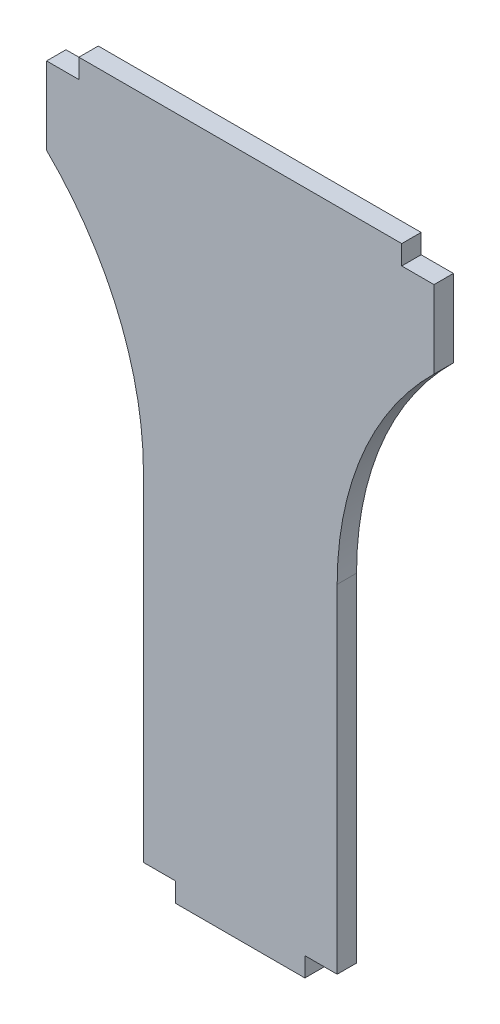
SolidWorks part; units mm, degrees
material "Acrylic (Medium-high impact)"
ref_plane "Plano frontal" through (0, 0, 0) normal (0, 0, 1) x (1, 0, 0)
ref_plane "Plano superior" through (0, 0, 0) normal (0, 1, 0) x (1, 0, 0)
ref_plane "Plano direito" through (0, 0, 0) normal (1, 0, 0) x (0, 0, -1)
sketch "Sketch2" plane through (0, 0, 0) normal (0, 0, 1) x (1, 0, 0)
  line L0 (15, 44) -> (30, 44)
  line L1 (10, -44) -> (15, -44)
  line L2 (-15, 44) -> (-15, -44)
  line L3 (-15, -44) -> (-10, -44)
  line L4 (15, 44) -> (15, -44)
  line L5 (-15, 44) -> (15, -44) construction
  line L6 (-15, -44) -> (15, 44) construction
  line L7 (-30, 56) -> (-25, 56)
  line L8 (-30, 56) -> (-30, 44)
  line L9 (-30, 44) -> (-15, 44)
  line L10 (30, 56) -> (30, 44)
  line L11 (-25, 59) -> (25, 59)
  line L12 (-25, 59) -> (-25, 56)
  line L14 (25, 59) -> (25, 56)
  line L16 (-10, -44) -> (-10, -47)
  line L17 (-10, -47) -> (10, -47)
  line L18 (10, -44) -> (10, -47)
  line L19 (25, 56) -> (30, 56)
  point P0 (0, 0)
  point P4 (0, 0)
  point P18 (0, 0)
  point P20 (0, 59)
  point P21 (0, -47)
  point P22 (0, 0)
  point P23 (0, 0)
  point P24 (0, 0)
  point P25 (0, 0)
  point P26 (15.1212, 43.1075)
  point P27 (18.0392, 59.9414)
  point P28 (-51.5495, 54.8194)
  dimension "D1" = 100
  dimension "D2" = 3
  dimension "D3" = 3
  dimension "D4" = 30
  dimension "D5" = 20
  dimension "D6" = 60
  dimension "D7" = 12
  dimension "D8" = 50
extrude "Boss-Extrude1" add sketch "Sketch2" along normal mid plane 3
fillet "Fillet1" radius 50 2 edges at (-15, 44, 0) (15, 44, 0)
